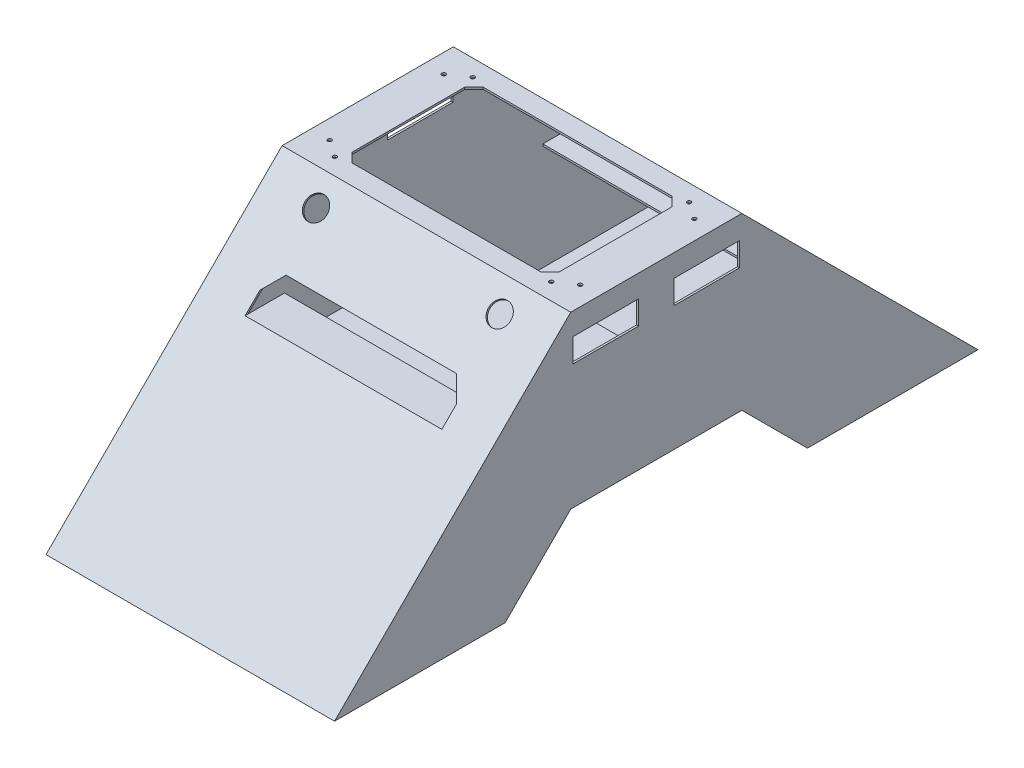
SolidWorks part; units mm, degrees
ref_plane "Front Plane" through (0, 0, 0) normal (0, 0, 1) x (1, 0, 0)
ref_plane "Top Plane" through (0, 0, 0) normal (0, 1, 0) x (1, 0, 0)
ref_plane "Right Plane" through (0, 0, 0) normal (1, 0, 0) x (0, 0, -1)
sketch "Sketch1" plane through (0, 0, 0) normal (0, 1, 0) x (1, 0, 0)
  line L1 (-110, 65.25) -> (110, 65.25)
  line L2 (-110, 65.25) -> (-110, -65.25)
  line L3 (-110, -65.25) -> (110, -65.25)
  line L4 (110, 65.25) -> (110, -65.25)
  line L5 (-110, 65.25) -> (110, -65.25) construction
  line L6 (-110, -65.25) -> (110, 65.25) construction
  point P0 (0, 0)
  dimension "D1" = 220
  dimension "D2" = 130.5
extrude "Boss-Extrude1" add sketch "Sketch1" along normal blind 3
sketch "Sketch5" plane through (0, 0, 0) normal (0, 1, 0) x (1, 0, 0)
  line L1 (-110, 65.25) -> (110, 65.25)
  line L2 (-110, 65.25) -> (-110, -65.25)
  line L3 (-110, -65.25) -> (110, -65.25)
  line L4 (110, 65.25) -> (110, -65.25)
  line L5 (-110, 65.25) -> (110, -65.25) construction
  line L6 (-110, -65.25) -> (110, 65.25) construction
  point P0 (0, 0)
  point P7 (0, 0)
extrude "Boss-Extrude2" add sketch "Sketch5" against normal blind 127
sketch "Sketch6" plane through (0, -127, 0) normal (0, -1, 0) x (1, 0, 0)
  line L1 (-110, 65.25) -> (110, 65.25)
  line L2 (-110, 65.25) -> (-110, -65.25)
  line L3 (-110, -65.25) -> (110, -65.25)
  line L4 (110, 65.25) -> (110, -65.25)
  line L5 (-110, 65.25) -> (110, -65.25) construction
  line L6 (-110, -65.25) -> (110, 65.25) construction
  point P0 (0, 0)
extrude "Boss-Extrude3" add sketch "Sketch6" against normal blind 1
sketch "Sketch8" plane through (0, 0, 0) normal (1, 0, 0) x (0, 0, -1)
  line L0 (-65.25, 3) -> (-65.25, -127)
  line L1 (-65.25, -127) -> (-115.25, -177)
  line L2 (-115.25, -177) -> (-245.25, -177)
  line L3 (-245.25, -177) -> (-65.25, 3)
  line L4 (-65.25, -127) -> (65.25, -127) construction
  line L5 (0, 99) -> (0, -99) construction
  line L6 (245.25, -177) -> (65.25, 3)
  line L7 (115.25, -177) -> (245.25, -177)
  line L8 (65.25, -127) -> (115.25, -177)
  line L9 (65.25, 3) -> (65.25, -127)
  dimension "D1" = 45
  dimension "D2" = 135
  dimension "D3" = 50
extrude "Boss-Extrude4" add sketch "Sketch8" along normal blind 110 and the other way blind 110
shell "Shell2" thickness 1.5
sketch "Sketch2" plane through (0, 0, 0) normal (0, 1, 0) x (1, 0, 0)
  line L0 (-99, 0) -> (99, 0) construction
  line L1 (0, -99) -> (0, 99) construction
  circle A0 centre (-82.5, 52.5) radius 1.5
  circle A1 centre (-82.5, -52.5) radius 1.5
  circle A2 centre (82.5, -52.5) radius 1.5
  circle A3 centre (82.5, 52.5) radius 1.5
  circle A4 centre (-95.5, 43.5) radius 1.5
  circle A5 centre (-95.5, -43.5) radius 1.5
  circle A6 centre (95.5, -43.5) radius 1.5
  circle A7 centre (95.5, 43.5) radius 1.5
  dimension "D1" = 82.5
  dimension "D2" = 52.5
  dimension "D3" = 3
  dimension "D4" = 3
  dimension "D5" = 43.5
  dimension "D6" = 95.5
extrude "Cut-Extrude1" cut sketch "Sketch2" along normal blind 3
sketch "Sketch4" plane through (0, 0, 0) normal (0, 1, 0) x (1, 0, 0)
  line L0 (-79, 42.9289) -> (-71.9289, 50)
  line L1 (-71.9289, 50) -> (71.9289, 50)
  line L2 (-79, 42.9289) -> (-79, -42.9289)
  line L3 (-71.9289, -50) -> (71.9289, -50)
  line L4 (79, 42.9289) -> (79, -42.9289)
  line L5 (-79, -42.9289) -> (-71.9289, -50)
  line L6 (71.9289, 50) -> (79, 42.9289)
  line L7 (71.9289, -50) -> (79, -42.9289)
  point P0 (0, 0)
  dimension "D1" = 45
  dimension "D2" = 10
  dimension "D3" = 10
  dimension "D4" = 79
  dimension "D5" = 50
  dimension "D6" = 45
  dimension "D7" = 100
  dimension "D8" = 158
  dimension "D9" = 10
  dimension "D10" = 10
  dimension "D11" = 45
  dimension "D12" = 45
extrude "Cut-Extrude2" cut sketch "Sketch4" along normal blind 10
sketch "Sketch7" plane through (0, 0, 0) normal (1, 0, 0) x (0, 0, -1)
  line L0 (-65.25, 3) -> (65.25, 3) construction
  line L1 (-63.5, -14) -> (-13.5, -14)
  line L2 (-63.5, -14) -> (-63.5, -32)
  line L3 (-63.5, -32) -> (-13.5, -32)
  line L4 (-13.5, -14) -> (-13.5, -32)
  line L5 (0, 99) -> (0, -99) construction
  line L6 (13.5, -14) -> (13.5, -32)
  line L7 (63.5, -32) -> (13.5, -32)
  line L8 (63.5, -14) -> (63.5, -32)
  line L9 (63.5, -14) -> (13.5, -14)
  dimension "D1" = 50
  dimension "D2" = 18
  dimension "D3" = 17
  dimension "D4" = 13.5
extrude "Cut-Extrude3" cut sketch "Sketch7" against normal through all both and the other way through all
sketch "Sketch9" plane through (0, 34.125, 34.125) normal (0, 0.7071, 0.7071) x (1, 0, 0)
  line L0 (-110, -44.0174) -> (110, -44.0174) construction
  line L1 (110, -44.0174) -> (110, -298.5758) construction
  line L2 (0, -99) -> (0, 99) construction
  circle A0 centre (70, -64.0174) radius 8.5
  circle A1 centre (-70, -64.0174) radius 8.5
  dimension "D1" = 17
  dimension "D2" = 20
  dimension "D3" = 40
extrude "Cut-Extrude4" cut sketch "Sketch9" against normal blind 10
sketch "Sketch10" plane through (0, 0, 0) normal (0, 0, 1) x (1, 0, 0)
  line L0 (-75, -49) -> (-65, -39)
  line L1 (-65, -39) -> (65, -39)
  line L2 (-75, -49) -> (-75, -60.2132)
  line L3 (-75, -60.2132) -> (75, -60.2132)
  line L4 (75, -49) -> (75, -60.2132)
  line L5 (65, -39) -> (75, -49)
  line L6 (-110, 3) -> (110, 3) construction
  dimension "D1" = 150
  dimension "D2" = 75
  dimension "D3" = 130
  dimension "D4" = 65
  dimension "D5" = 21.2132
  dimension "D6" = 42
  dimension "D7" = 10
  dimension "D8" = 10
extrude "Cut-Extrude5" cut sketch "Sketch10" along normal through all both and the other way through all
sketch "Sketch11" plane through (0, -60.2132, 0) normal (0, 1, 0) x (1, 0, 0)
  line L1 (-75, -128.4632) -> (75, -128.4632)
  line L2 (-75, -128.4632) -> (-75, -98.4632)
  line L3 (-75, -98.4632) -> (75, -98.4632)
  line L4 (75, -128.4632) -> (75, -98.4632)
  line L5 (-75, 128.4632) -> (75, 128.4632)
  line L6 (-75, 128.4632) -> (-75, 98.4632)
  line L7 (-75, 98.4632) -> (75, 98.4632)
  line L8 (75, 128.4632) -> (75, 98.4632)
  dimension "D1" = 150
  dimension "D2" = 30
  dimension "D3" = 30
  dimension "D4" = 150
extrude "Boss-Extrude5" add sketch "Sketch11" against normal blind 1.5
sketch "Sketch12" plane through (0, 19.99, -48.26) normal (0, -0.7071, 0.7071) x (1, 0, 0)
  line L3 (110, -278.5859) -> (110, -24.0274) construction
  line L4 (110, -24.0274) -> (-110, -24.0274) construction
  line L5 (-110, -278.5859) -> (-110, -24.0274) construction
  circle A0 centre (70, -44.0274) radius 8.5
  circle A1 centre (-70, -44.0274) radius 8.5
  dimension "D1" = 17
  dimension "D2" = 40
  dimension "D3" = 20
  dimension "D4" = 20
  dimension "D5" = 40
  dimension "D6" = 17
extrude "Cut-Extrude6" cut sketch "Sketch12" along normal blind 1.5
